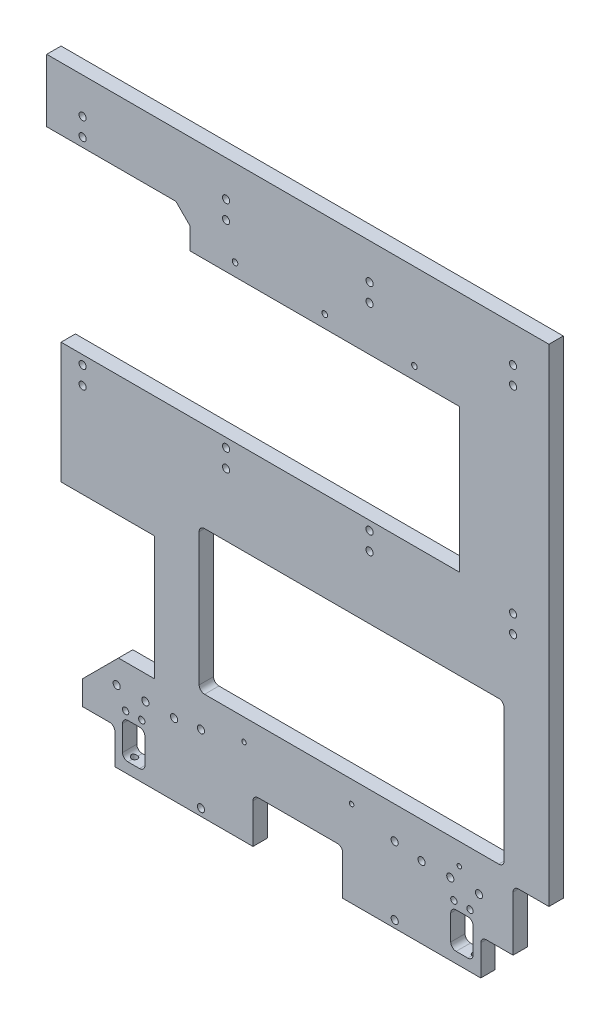
SolidWorks part; units mm, degrees
ref_plane "Front" through (0, 0, 0) normal (0, 0, 1) x (1, 0, 0)
ref_plane "Top" through (0, 0, 0) normal (0, 1, 0) x (1, 0, 0)
ref_plane "Right" through (0, 0, 0) normal (1, 0, 0) x (0, 0, -1)
sketch "Esquisse1" plane through (0, 0, 0) normal (0, 0, 1) x (1, 0, 0)
  line L1 (0, 0) -> (280, 0)
  line L2 (0, 0) -> (0, 45)
  line L3 (0, 45) -> (280, 45)
  line L4 (280, 0) -> (280, 45)
  dimension "D1" = 280
  dimension "D2" = 45
extrude "Boss.-Extru.1" add sketch "Esquisse1" along normal blind 8
sketch "Esquisse3" plane through (0, 0, 8) normal (0, 0, 1) x (1, 0, 0)
  line L0 (140, 0) -> (140, 32.6648) construction
  line L1 (0, 0) -> (38, 0)
  line L2 (0, 0) -> (0, 20)
  line L3 (0, 20) -> (38, 20)
  line L4 (38, 0) -> (38, 20)
  line L5 (0, 0) -> (280, 0) construction
  line L6 (242, 0) -> (242, 20)
  line L7 (280, 20) -> (242, 20)
  line L8 (280, 0) -> (280, 20)
  line L9 (280, 0) -> (242, 0)
  dimension "D1" = 20
  dimension "D2" = 38
extrude "Enlèv. mat.-Extru.2" cut sketch "Esquisse3" against normal through all
sketch "Esquisse2" plane through (0, 0, 8) normal (0, 0, 1) x (1, 0, 0)
  line L0 (140, 0) -> (140, 45) construction
  line L1 (38, 0) -> (242, 0) construction
  line L2 (280, 45) -> (0, 45) construction
  line L3 (86, 4) -> (86, 42) construction
  line L4 (194, 4) -> (194, 42) construction
  circle A0 centre (86, 4) radius 2
  circle A1 centre (86, 42) radius 2
  circle A2 centre (194, 42) radius 2
  circle A3 centre (194, 4) radius 2
  dimension "D1" = 4
  dimension "D3" = 4
  dimension "D2" = 54
  dimension "D4" = 38
extrude "Enlèv. mat.-Extru.1" cut sketch "Esquisse2" against normal through all
sketch "Esquisse4" plane through (0, 0, 8) normal (0, 0, 1) x (1, 0, 0)
  line L0 (39, 40) -> (71, 40) construction
  line L1 (140, 0) -> (140, 45) construction
  line L2 (38, 0) -> (242, 0) construction
  line L3 (280, 45) -> (0, 45) construction
  line L4 (241, 40) -> (209, 40) construction
  line L5 (236, 30) -> (227, 30) construction
  line L6 (44, 30) -> (53, 30) construction
  line L7 (231.5, 26) -> (231.5, 30) construction
  line L8 (225.25, 26) -> (237.75, 26)
  line L9 (225.25, 26) -> (225.25, 6)
  line L10 (225.25, 6) -> (237.75, 6)
  line L11 (237.75, 26) -> (237.75, 6)
  line L12 (42.25, 26) -> (42.25, 6)
  line L13 (54.75, 6) -> (42.25, 6)
  line L14 (54.75, 26) -> (54.75, 6)
  line L15 (54.75, 26) -> (42.25, 26)
  circle A0 centre (71, 40) radius 2
  circle A1 centre (39, 40) radius 2
  circle A2 centre (55, 40) radius 2
  circle A3 centre (225, 40) radius 2
  circle A4 centre (241, 40) radius 2
  circle A5 centre (209, 40) radius 2
  circle A6 centre (236, 30) radius 1.75
  circle A7 centre (227, 30) radius 1.75
  circle A9 centre (53, 30) radius 1.75
  circle A10 centre (44, 30) radius 1.75
  circle A11 centre (194, 4) radius 2 construction
  dimension "D1" = 4
  dimension "D2" = 16
  dimension "D5" = 3.5
  dimension "D7" = 33
  dimension "D3" = 40
  dimension "D4" = 170
  dimension "D6" = 9
  dimension "D8" = 30
  dimension "D9" = 20
  dimension "D10" = 12.5
  dimension "D11" = 4
extrude "Enlèv. mat.-Extru.3" cut sketch "Esquisse4" against normal through all
sketch "Esquisse5" plane through (0, 0, 0) normal (0, -1, 0) x (-1, 0, 0)
  line L0 (-38, -4) -> (-242, -4) construction
  line L1 (-38, 0) -> (-38, -8) construction
  line L2 (-242, 0) -> (-242, -8) construction
  line L3 (-140, -4) -> (-140, -7.2082) construction
  circle A0 centre (-180, -4) radius 1.65
  circle A1 centre (-235, -4) radius 1.65
  circle A2 centre (-45, -4) radius 1.65
  circle A3 centre (-100, -4) radius 1.65
  dimension "D1" = 3.3
  dimension "D2" = 95
  dimension "D3" = 80
extrude "Enlèv. mat.-Extru.4" cut sketch "Esquisse5" against normal blind 10
sketch "Esquisse6" plane through (0, 0, 0) normal (0, 0, -1) x (-1, 0, 0)
  line L0 (-38, 0) -> (-242, 0) construction
  line L1 (-165, 25) -> (-115, 25)
  line L2 (-165, 25) -> (-165, 0)
  line L3 (-165, 0) -> (-115, 0)
  line L4 (-115, 25) -> (-115, 0)
  line L5 (-140, 25) -> (-140, 45) construction
  line L6 (-280, 45) -> (0, 45) construction
  dimension "D1" = 50
  dimension "D2" = 25
extrude "Enlèv. mat.-Extru.5" cut sketch "Esquisse6" against normal through all
sketch "Esquisse7" plane through (0, 0, 8) normal (0, 0, 1) x (1, 0, 0)
  line L0 (0, 45) -> (280, 45)
  line L1 (280, 45) -> (280, 325)
  line L2 (280, 325) -> (0, 325)
  line L3 (0, 325) -> (0, 45)
  dimension "D1" = 280
extrude "Boss.-Extru.2" add sketch "Esquisse7" against normal up to vertex (8 mm away) up to point (0, 45, 0)
sketch "Esquisse8" plane through (0, 0, 8) normal (0, 0, 1) x (1, 0, 0)
  line L1 (85, 140) -> (255, 140)
  line L2 (85, 140) -> (85, 60)
  line L3 (85, 60) -> (255, 60)
  line L4 (255, 140) -> (255, 60)
  line L5 (280, 20) -> (280, 325) construction
  line L6 (38, 0) -> (115, 0) construction
  dimension "D1" = 80
  dimension "D2" = 170
  dimension "D3" = 25
  dimension "D4" = 60
extrude "Enlèv. mat.-Extru.6" cut sketch "Esquisse8" against normal through all
sketch "Esquisse9" plane through (0, 0, 8) normal (0, 0, 1) x (1, 0, 0)
  line L0 (0, 325) -> (0, 20) construction
  line L1 (0, 53.5) -> (60, 53.5)
  line L2 (0, 53.5) -> (0, 122.5)
  line L3 (0, 122.5) -> (60, 122.5)
  line L4 (60, 53.5) -> (60, 122.5)
  line L5 (38, 0) -> (115, 0) construction
  dimension "D1" = 60
  dimension "D2" = 69
  dimension "D3" = 53.5
extrude "Enlèv. mat.-Extru.7" cut sketch "Esquisse9" against normal through all
sketch "Esquisse10" plane through (0, 0, 8) normal (0, 0, 1) x (1, 0, 0)
  line L0 (0, 53.5) -> (60, 53.5) construction
  line L1 (0, 20) -> (20, 20)
  line L2 (0, 20) -> (0, 53.5)
  line L3 (0, 53.5) -> (20, 53.5)
  line L4 (20, 20) -> (20, 53.5)
  line L5 (140, 325) -> (140, 248.098) construction
  line L6 (280, 325) -> (0, 325) construction
  line L7 (260, 20) -> (260, 53.5)
  line L8 (280, 53.5) -> (260, 53.5)
  line L9 (280, 20) -> (280, 53.5)
  line L10 (280, 20) -> (260, 20)
  dimension "D1" = 20
extrude "Enlèv. mat.-Extru.8" cut sketch "Esquisse10" against normal through all
chamfer "Chanfrein1" distance 20 angle 45 1 edges at (20, 53.5, 4)
fillet "Congé1" radius 3 17 edges at (242, 20, 4) (237.75, 6, 4) (237.75, 26, 4) (225.25, 26, 4) (225.25, 6, 4) (54.75, 26, 4) (54.75, 6, 4) (42.25, 6, 4) (42.25, 26, 4) (38, 20, 4) (115, 25, 4) (165, 25, 4) (260, 53.5, 4) (85, 140, 4) (255, 140, 4) (255, 60, 4) (85, 60, 4)
sketch "Esquisse11" plane through (0, 0, 8) normal (0, 0, 1) x (1, 0, 0)
  line L1 (0, 270) -> (230, 270)
  line L2 (0, 270) -> (0, 190)
  line L3 (0, 190) -> (230, 190)
  line L4 (230, 270) -> (230, 190)
  line L6 (38, 0) -> (115, 0) construction
  line L7 (0, 325) -> (0, 122.5) construction
  dimension "D1" = 80
  dimension "D2" = 190
  dimension "D3" = 230
extrude "Enlèv. mat.-Extru.9" cut sketch "Esquisse11" against normal through all
sketch "Esquisse12" plane through (0, 0, 8) normal (0, 0, 1) x (1, 0, 0)
  line L2 (0, 290) -> (80, 290)
  line L3 (0, 290) -> (0, 270)
  line L4 (0, 270) -> (80, 270)
  line L5 (80, 290) -> (80, 270)
  point P5 (83.4649, 284.2018)
  point P6 (0, 0)
  point P7 (0, 270)
  dimension "D1" = 80
  dimension "D2" = 20
extrude "Enlèv. mat.-Extru.10" cut sketch "Esquisse12" against normal through all
sketch "Esquisse13" plane through (0, 0, 8) normal (0, 0, 1) x (1, 0, 0)
  line L0 (0, 190) -> (230, 190) construction
  line L1 (0, 122.5) -> (8, 122.5)
  line L2 (0, 122.5) -> (0, 190)
  line L3 (0, 190) -> (8, 190)
  line L4 (8, 122.5) -> (8, 190)
  dimension "D1" = 8
extrude "Enlèv. mat.-Extru.11" cut sketch "Esquisse13" against normal through all
sketch "Esquisse14" plane through (0, 0, 8) normal (0, 0, 1) x (1, 0, 0)
  line L0 (20, 190) -> (20, 290) construction
  line L1 (8, 190) -> (230, 190) construction
  line L2 (80, 290) -> (0, 290) construction
  line L3 (20, 240) -> (13.6887, 240) construction
  line L4 (20, 175) -> (20, 185) construction
  line L5 (20, 305) -> (20, 295) construction
  line L7 (100, 190) -> (100, 290) construction
  line L8 (100, 240) -> (93.6887, 240) construction
  line L9 (100, 175) -> (100, 185) construction
  line L10 (100, 305) -> (100, 295) construction
  line L11 (180, 190) -> (180, 290) construction
  line L12 (180, 240) -> (173.6887, 240) construction
  line L13 (180, 175) -> (180, 185) construction
  line L14 (180, 305) -> (180, 295) construction
  line L15 (93.6887, 240) -> (20, 240) construction
  line L16 (110, 48) -> (170, 48) construction
  line L17 (170, 48) -> (170, 60) construction
  line L18 (88, 60) -> (252, 60) construction
  line L19 (260, 190) -> (260, 290) construction
  line L20 (260, 240) -> (253.6887, 240) construction
  line L21 (260, 175) -> (260, 185) construction
  line L22 (260, 305) -> (260, 295) construction
  line L23 (100, 240) -> (180, 240) construction
  line L24 (180, 240) -> (140, 240) construction
  line L25 (140, 240) -> (140, 325) construction
  line L26 (280, 325) -> (0, 325) construction
  circle A0 centre (20, 185) radius 2
  circle A1 centre (20, 175) radius 2
  circle A2 centre (20, 305) radius 2
  circle A3 centre (20, 295) radius 2
  circle A4 centre (100, 185) radius 2
  circle A5 centre (100, 175) radius 2
  circle A6 centre (100, 305) radius 2
  circle A7 centre (100, 295) radius 2
  circle A8 centre (180, 185) radius 2
  circle A9 centre (180, 175) radius 2
  circle A10 centre (180, 305) radius 2
  circle A11 centre (180, 295) radius 2
  circle A12 centre (110, 48) radius 1.25
  circle A13 centre (170, 48) radius 1.25
  circle A14 centre (230, 48) radius 1.25
  circle A15 centre (260, 185) radius 2
  circle A16 centre (260, 175) radius 2
  circle A17 centre (260, 305) radius 2
  circle A18 centre (260, 295) radius 2
  dimension "D1" = 4
  dimension "D2" = 10
  dimension "D8" = 2.5
  dimension "D3" = 130
  dimension "D6" = 80
  dimension "D7" = 60
  dimension "D9" = 12
  dimension "D5" = 4
extrude "Enlèv. mat.-Extru.12" cut sketch "Esquisse14" against normal through all
sketch "Esquisse15" plane through (0, 0, 0) normal (0, 0, -1) x (-1, 0, 0)
  line L0 (-80, 270) -> (-80, 290) construction
  line L1 (-230, 280.1) -> (-80, 280.1)
  line L2 (-230, 280.1) -> (-230, 274)
  line L3 (-230, 274) -> (-80, 274)
  line L4 (-80, 280.1) -> (-80, 274)
  line L5 (-230, 270) -> (-80, 270) construction
  dimension "D1" = 6.1
  dimension "D2" = 4
  dimension "D3" = 150
extrude "Enlèv. mat.-Extru.13" cut sketch "Esquisse15" against normal blind 2
sketch "Esquisse16" plane through (0, 0, 2) normal (0, 0, -1) x (-1, 0, 0)
  line L0 (-230, 277.05) -> (-80, 277.05) construction
  line L1 (-230, 280.1) -> (-230, 274) construction
  line L2 (-80, 274) -> (-80, 280.1) construction
  line L3 (-155, 277.05) -> (-155, 299.1908) construction
  circle A0 centre (-155, 277.05) radius 1.55
  circle A1 centre (-205, 277.05) radius 1.55
  circle A2 centre (-105, 277.05) radius 1.55
  dimension "D1" = 3.1
  dimension "D2" = 50
extrude "Enlèv. mat.-Extru.14" cut sketch "Esquisse16" against normal through all
chamfer "Chanfrein2" distance 8 angle 45 1 edges at (80, 290, 4)
